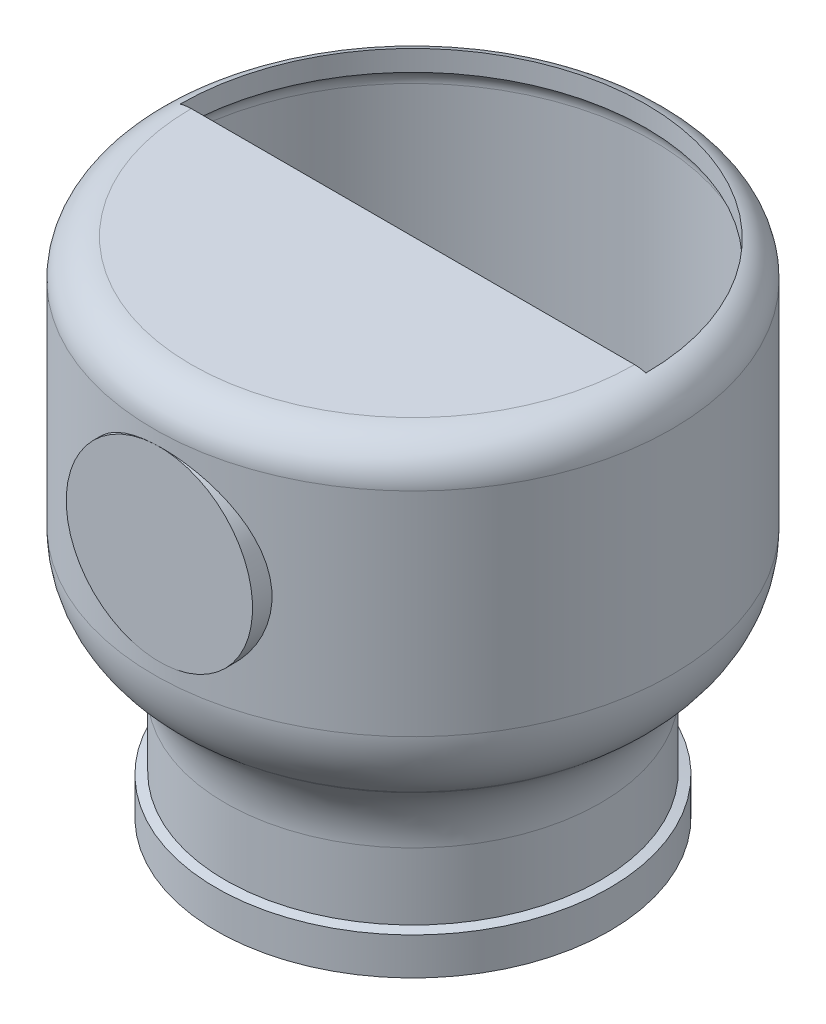
SolidWorks part; units mm, degrees
ref_plane "Front Plane" through (0, 0, 0) normal (0, 0, 1) x (1, 0, 0)
ref_plane "Top Plane" through (0, 0, 0) normal (0, 1, 0) x (1, 0, 0)
ref_plane "Right Plane" through (0, 0, 0) normal (1, 0, 0) x (0, 0, -1)
sketch "Sketch1" plane through (0, 0, 0) normal (0, 0, 1) x (1, 0, 0)
  line L0 (2.7649, 7.8218) -> (2.7649, 58.3592) construction
  line L1 (20.9, 0) -> (23.8716, 0)
  line L2 (23.8716, 0) -> (23.8716, 4)
  line L3 (23.8716, 4) -> (22.9, 4.2367)
  line L4 (22.9, 4.2367) -> (22.9, 11.4043)
  line L6 (20.9, 0) -> (20.9, 14)
  line L8 (2.7649, 52) -> (2.7649, 54)
  line L10 (17.2603, 17) -> (2.7649, 17)
  line L12 (19.9, 15) -> (2.7649, 15)
  line L13 (2.7649, 17) -> (2.7649, 15)
  line L15 (23.6882, 19.3396) -> (24.9883, 20.4305)
  line L16 (28.5604, 28.091) -> (28.5604, 50)
  line L17 (26.4721, 19.0648) -> (26.9883, 19.4979)
  line L18 (30.5604, 27.1583) -> (30.5604, 50)
  line L19 (26.5604, 52) -> (2.7649, 52)
  line L20 (26.5604, 54) -> (2.7649, 54)
  arc A0 (28.5604, 50) -> (26.5604, 52) centre (26.5604, 50) ccw
  arc A1 (30.5604, 50) -> (26.5604, 54) centre (26.5604, 50) ccw
  arc A2 (26.4721, 19.0648) -> (22.9, 11.4043) centre (32.9, 11.4043) ccw
  arc A3 (26.9883, 19.4979) -> (30.5604, 27.1583) centre (20.5604, 27.1583) ccw
  arc A4 (24.9883, 20.4305) -> (28.5604, 28.091) centre (18.5604, 28.091) ccw
  arc A5 (17.2603, 17) -> (23.6882, 19.3396) centre (17.2603, 27) ccw
  arc A6 (20.9, 14) -> (19.9, 15) centre (19.9, 14) ccw
  point P11 (22.9, 54)
  point P28 (28.5604, 23.4279)
  point P31 (20.9, 17)
  dimension "D8" = 2
  dimension "D9" = 4
  dimension "D4" = 2
  dimension "D16" = 10
  dimension "D17" = 10
  dimension "D18" = 10
  dimension "D19" = 1
  dimension "D1" = 2
  dimension "D2" = 4
  dimension "D3" = 1
  dimension "D5" = 140
  dimension "D6" = 2
  dimension "D7" = 2.9716
  dimension "D10" = 2
  dimension "D11" = 15
  dimension "D12" = 35
  dimension "D13" = 37
  dimension "D14" = 2
  dimension "D15" = 10
revolve "Revolve1" add sketch "Sketch1" angle 360 about L0
ref_plane "Plane1" through (0, 4, 0) normal (0, 1, 0) x (1, 0, 0)
sketch "Sketch3" plane through (0, 0, 0) normal (0, 0, 1) x (1, 0, 0)
  point P0 (1.2404, 19.1989)
ref_point "Point1"
ref_plane "Plane2" through (0, 0, 22.9) normal (0, 0, 1) x (1, 0, 0)
ref_plane "Plane3" through (0, 0, 27.7955) normal (0, 0, 1) x (1, 0, 0)
ref_plane "Plane4" through (0, 54, 0) normal (0, 1, 0) x (1, 0, 0)
sketch "Sketch9" plane through (0, 54, 0) normal (0, 1, 0) x (1, 0, 0)
  line L0 (-22.2351, 0) -> (27.7649, 0)
  arc A0 (27.7649, 0) -> (-22.2351, 0) centre (2.7649, 0) ccw
  circle A3 centre (2.7649, 0) radius 23.7955 construction
  point P1 (0, 0)
  dimension "D1" = 50
  dimension "D3" = 25
  dimension "D4" = 0
extrude "Cut-Extrude2" cut sketch "Sketch9" against normal blind 25
sketch "Sketch10" plane through (0, 0, 27.7955) normal (0, 0, 1) x (1, 0, 0)
  line L0 (30.5604, 27.1583) -> (-25.0306, 27.1583) construction
  circle A0 centre (3.3463, 38.6583) radius 10
  dimension "D1" = 20
  dimension "D2" = 11.5
extrude "Boss-Extrude1" add sketch "Sketch10" against normal blind 5
ref_plane "Plane5" through (0, 17, 0) normal (0, 1, 0) x (1, 0, 0)
sketch "Sketch11" plane through (0, 17, 0) normal (0, 1, 0) x (1, 0, 0)
  line L0 (-14.7351, 0) -> (20.2649, 0)
  arc A1 (-14.7351, 0) -> (20.2649, 0) centre (2.7649, 0) cw
  circle A2 centre (2.7649, 0) radius 20.9233 construction
  point P6 (0, 0)
  point P7 (0, 0)
  point P8 (0, 0)
  point P9 (0, 0)
  point P10 (0, 0)
  dimension "D2" = 0
  dimension "D1" = 35
extrude "Cut-Extrude3" cut sketch "Sketch11" against normal blind 10 and the other way blind 5
